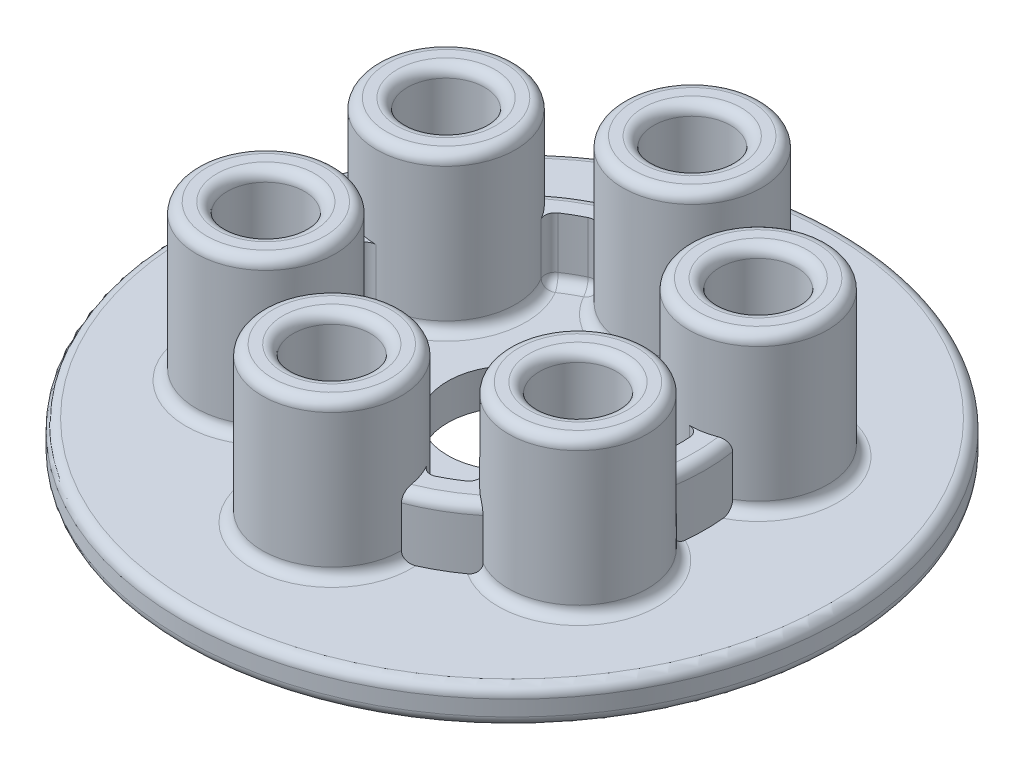
SolidWorks part; units mm, degrees
ref_plane "Front" through (0, 0, 0) normal (0, 0, 1) x (1, 0, 0)
ref_plane "Top" through (0, 0, 0) normal (0, 1, 0) x (1, 0, 0)
ref_plane "Right" through (0, 0, 0) normal (1, 0, 0) x (0, 0, -1)
sketch "Sketch1" plane through (0, 0, 0) normal (0, 1, 0) x (1, 0, 0)
  circle A0 centre (0, 0) radius 64
  dimension "D1" = 128
extrude "Boss-Extrude1" add sketch "Sketch1" along normal blind 7
sketch "Sketch2" plane through (0, 7, 0) normal (0, 1, 0) x (1, 0, 0)
  circle A0 centre (0, 0) radius 37.5
  circle A1 centre (0, 0) radius 32.5
  dimension "D1" = 75
  dimension "D2" = 5
extrude "Boss-Extrude2" add sketch "Sketch2" along normal blind 12
sketch "Sketch3" plane through (0, 7, 0) normal (0, 1, 0) x (1, 0, 0)
  circle A0 centre (0, 0) radius 12.5
  dimension "D1" = 25
extrude "Cut-Extrude1" cut sketch "Sketch3" against normal through all
fillet "Fillet2" radius 2 3 edges at (0, 0, 64) (0, 7, 64) (0, 19, 37.5)
sketch "Sketch4" plane through (0, 7, 0) normal (0, 1, 0) x (1, 0, 0)
  line L0 (0, 0) -> (0, 35) construction
  circle A0 centre (0, 35) radius 13.5
  point P4 (0, 0)
  point P5 (0, 0)
  point P6 (0, 0)
  point P7 (0, 0)
  dimension "D1" = 27
extrude "Boss-Extrude3" add sketch "Sketch4" along normal blind 30
sketch "Sketch5" plane through (0, 37, 0) normal (0, 1, 0) x (1, 0, 0)
  circle A0 centre (0, 35) radius 7.5
  dimension "D1" = 15
extrude "Cut-Extrude2" cut sketch "Sketch5" against normal through all
fillet "Fillet3" radius 2 5 edges at (0, 37, -21.5) (0, 37, -27.5) (0, 0, -27.5) (-12.5342, 13, -29.9857) (12.5342, 13, -29.9857)
pattern_circular "CirPattern2" count 6 over 360 about axis through (0, 19, 0) along (0, -1, 0) of "Boss-Extrude3", "Cut-Extrude2", "Fillet3"
fillet "Fillet4" radius 2 30 edges at (-12.8963, 7, -29.2686) (-16.25, 7, -28.1458) (-18.8992, 7, -25.8029) (-18.6195, 7, -10.75) (-31.7955, 7, -3.4658) (-32.5, 7, 0) (-31.7955, 7, 3.4658) (-18.6195, 7, 10.75) (-18.8992, 7, 25.8029) (-16.25, 7, 28.1458) (-12.8963, 7, 29.2686) (0, 7, 21.5) (12.8963, 7, 29.2686) (16.25, 7, 28.1458) (18.8992, 7, 25.8029) (18.6195, 7, 10.75) (31.7955, 7, 3.4658) (32.5, 7, 0) (31.7955, 7, -3.4658) (18.6195, 7, -10.75) (18.8992, 7, -25.8029) (16.25, 7, -28.1458) (12.8963, 7, -29.2686) (0, 7, -21.5) (-42.0022, 7, 24.25) (42.0022, 7, -24.25) (0, 7, 48.5) (0, 7, -48.5) (-42.0022, 7, -24.25) (42.0022, 7, 24.25)
